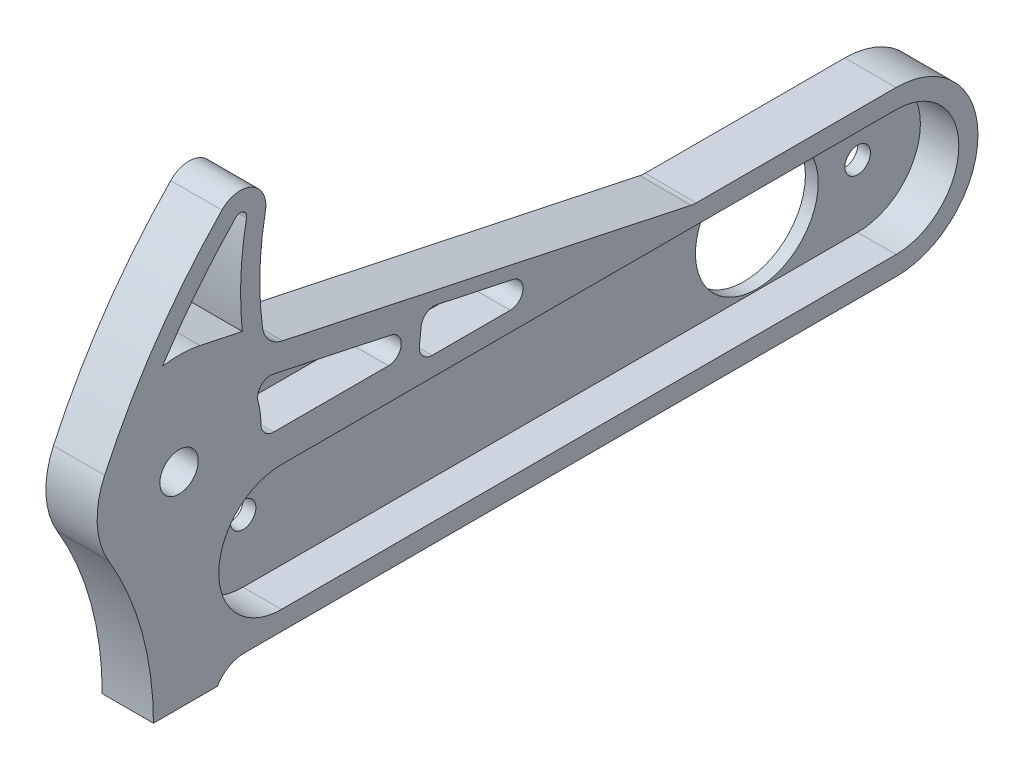
SolidWorks part; units mm, degrees
material "UHMW Polyethylene"
ref_plane "Front Plane" through (0, 0, 0) normal (0, 0, 1) x (1, 0, 0)
ref_plane "Top Plane" through (0, 0, 0) normal (0, 1, 0) x (1, 0, 0)
ref_plane "Right Plane" through (0, 0, 0) normal (1, 0, 0) x (0, 0, -1)
ref_plane "Plane1" through (44.45, 0, 0) normal (1, 0, 0) x (0, 0, -1)
sketch "Sketch1" plane through (44.45, 0, 0) normal (1, 0, 0) x (0, 0, -1)
  line L0 (0, 20.32) -> (-50.1918, 20.32)
  line L1 (-50.1918, 20.32) -> (-156.3872, 42.8925)
  line L2 (-184.15, -24.13) -> (-168.275, -24.13)
  line L3 (-177.8, -24.13) -> (-177.8, 26.67) construction
  line L4 (-161.6759, -20.32) -> (0, -20.32)
  line L5 (-210.1467, 95.3503) -> (7.8853, 24.145) construction
  line L6 (0, -25.4) -> (-249.5816, -25.4) construction
  arc A0 (-195.2627, 16.2798) -> (-196.2562, 35.1713) centre (-177.8, 26.67) cw
  arc A1 (-196.2562, 35.1713) -> (-167.1767, 77.5725) centre (-57.8348, -28.5883) cw
  arc A2 (-167.1767, 77.5725) -> (-156.3872, 71.9389) centre (-162.6208, 73.1492) cw
  arc A4 (-184.15, -24.13) -> (-195.2627, 16.2798) centre (-263.1786, -24.13) ccw
  arc A6 (-168.275, -24.13) -> (-161.6759, -20.32) centre (-161.6759, -27.94) cw
  arc A7 (0, -20.32) -> (0, 20.32) centre (0, 0) ccw
  circle A8 centre (0, 0) radius 25.4 construction
  circle A9 centre (-177.8, 26.67) radius 52.07 construction
  circle A10 centre (-161.6351, 76.1673) radius 3.175 construction
  arc A11 (-156.3872, 71.9389) -> (-156.3872, 42.8925) centre (-81.584, 57.4157) ccw
  circle A12 centre (-177.8, 26.67) radius 4.7625
  circle A13 centre (-152.4, 0) radius 3.175
  circle A14 centre (0, 0) radius 3.175
  circle A15 centre (-25.0031, 0) radius 15.22
  circle A17 centre (-25.0031, 0) radius 13.95 construction
  dimension "D1" = 6.35
  dimension "D2" = 152.4
  dimension "D3" = 76.2
  dimension "D6" = 7.62
  dimension "D9" = 5.08
  dimension "D10" = 31.75
  dimension "D12" = 9.525
  dimension "D13" = 6.35
  dimension "D8" = 1.27
  dimension "D4" = 15.875
  dimension "D5" = 6.35
  dimension "D7" = 12
  dimension "D11" = 1.27
extrude "Boss-Extrude1" add sketch "Sketch1" along normal blind 12.7
sketch "Sketch6" plane through (57.15, 0, 0) normal (1, 0, 0) x (0, 0, -1)
  line L0 (-35.4758, -20.32) -> (-14.5304, -20.32)
  line L1 (-35.4758, 20.32) -> (-14.5304, 20.32)
  line L2 (0, 20.32) -> (-50.1918, 20.32) construction
  line L3 (-161.6759, -20.32) -> (0, -20.32) construction
  arc A0 (-35.4758, -20.32) -> (-14.5304, -20.32) centre (-25.0031, 0) ccw
  circle A1 centre (-25.0031, 0) radius 15.22 construction
  arc A2 (-14.5304, 20.32) -> (-35.4758, 20.32) centre (-25.0031, 0) ccw
  dimension "D1" = 22.86
extrude "28mm motor support" [suppressed] add sketch "Sketch6" against normal up to surface (12.7 mm away) up to face at (44.45, 18.3967, 128.7869)
sketch "Sketch4" plane through (57.15, 0, 0) normal (1, 0, 0) x (0, 0, -1)
  line L0 (-157.7296, 23.495) -> (-95.6708, 23.495)
  line L1 (-95.6708, 23.495) -> (-160.4619, 37.2668)
  line L3 (-50.1918, 20.32) -> (-156.3872, 42.8925) construction
  line L4 (0, 20.32) -> (-50.1918, 20.32) construction
  arc A0 (-160.4619, 37.2668) -> (-157.7296, 23.495) centre (-177.8, 26.67) cw
  arc A2 (-196.2562, 35.1713) -> (-195.2627, 16.2798) centre (-177.8, 26.67) ccw construction
  dimension "D1" = 3.175
  dimension "D2" = 6.35
extrude "Cut-Extrude3" cut sketch "Sketch4" against normal offset from surface (10.16 mm away) 2.54 up to face at (44.45, 18.3967, 128.7869)
fillet "Fillet2" radius 3.175 3 edges at (52.07, 23.495, 95.6708) (52.07, 23.495, 157.7296) (52.07, 37.2668, 160.4619)
sketch "Sketch5" plane through (57.15, 0, 0) normal (1, 0, 0) x (0, 0, -1)
  line L0 (-113.9556, 30.6275) -> (-95.0107, 26.6006)
  line L1 (-95.6708, 20.32) -> (-115.0389, 20.32)
  line L2 (0, 20.32) -> (-50.1918, 20.32) construction
  line L3 (-50.1918, 20.32) -> (-156.3872, 42.8925) construction
  line L4 (-117.7733, 27.8537) -> (-118.1965, 23.8269)
  line L5 (-95.6708, 23.495) -> (-125.8789, 26.67) construction
  arc A0 (-113.9556, 30.6275) -> (-117.7733, 27.8537) centre (-114.6157, 27.5219) ccw
  arc A1 (-118.1965, 23.8269) -> (-115.0389, 20.32) centre (-115.0389, 23.495) ccw
  arc A2 (-95.6708, 20.32) -> (-95.0107, 26.6006) centre (-95.6708, 23.495) ccw
  arc A4 (-125.8789, 23.495) -> (-125.2188, 29.7756) centre (-125.8789, 26.67) ccw construction
  point P20 (-122.7213, 26.3381)
  dimension "D2" = 3.175
  dimension "D1" = 3.175
  dimension "D3" = 4.7625
extrude "Cut-Extrude4" cut sketch "Sketch5" against normal up to surface (10.16 mm away) up to face at (46.99, 28.5995, 145.7216)
sketch "Sketch2" plane through (57.15, 0, 0) normal (1, 0, 0) x (0, 0, -1)
  line L0 (-173.5752, 46.546) -> (-156.3872, 42.8925)
  line L1 (-172.5851, 51.2044) -> (-162.1055, 48.9769)
  arc A0 (-196.2562, 35.1713) -> (-173.5752, 46.546) centre (-177.8, 26.67) cw
  arc A1 (-196.2562, 35.1713) -> (-195.2627, 16.2798) centre (-177.8, 26.67) ccw construction
  arc A2 (-167.1767, 77.5725) -> (-196.2562, 35.1713) centre (-57.8348, -28.5883) ccw construction
  arc A3 (-156.3872, 71.9389) -> (-156.3872, 42.8925) centre (-81.584, 57.4157) ccw construction
  arc A4 (-156.3872, 71.9389) -> (-167.1767, 77.5725) centre (-162.6208, 73.1492) ccw construction
  arc A5 (-156.3872, 71.9389) -> (-156.3872, 42.8925) centre (-81.584, 57.4157) ccw
  arc A6 (-156.3872, 71.9389) -> (-167.1767, 77.5725) centre (-162.6208, 73.1492) ccw
  arc A7 (-167.1767, 77.5725) -> (-196.2562, 35.1713) centre (-57.8348, -28.5883) ccw
  arc A8 (-161.0624, 72.8466) -> (-162.1055, 48.9769) centre (-81.584, 57.4157) ccw
  arc A9 (-161.0624, 72.8466) -> (-163.7597, 74.255) centre (-162.6208, 73.1492) ccw
  arc A10 (-163.7597, 74.255) -> (-181.9186, 51.4121) centre (-57.8348, -28.5883) ccw
  arc A11 (-181.9186, 51.4121) -> (-172.5851, 51.2044) centre (-177.8, 26.67) cw
  dimension "D1" = 4.7625
extrude "Cut-Extrude1" cut sketch "Sketch2" against normal up to surface (12.7 mm away) contours A10 A11 L1 A8 A9 region at (57.15, 59.6657, 168.7495) up to face at (44.45, 18.3967, 128.7869)
sketch "Sketch3" plane through (57.15, 0, 0) normal (1, 0, 0) x (0, 0, -1)
  line L0 (-152.4, 15.5575) -> (0, 15.5575)
  line L1 (0, -15.5575) -> (-152.4, -15.5575)
  line L2 (0, 20.32) -> (-50.1918, 20.32) construction
  arc A0 (0, 15.5575) -> (0, -15.5575) centre (0, 0) cw
  arc A1 (-152.4, -15.5575) -> (-152.4, 15.5575) centre (-152.4, 0) cw
  arc A3 (0, -20.32) -> (0, 20.32) centre (0, 0) ccw construction
  circle A4 centre (-152.4, 0) radius 25.4 construction
  dimension "D1" = 4.7625
extrude "Cut-Extrude2" cut sketch "Sketch3" against normal offset from surface (9.525 mm away) 3.175 up to face at (44.45, 18.3967, 128.7869)
fillet "Fillet1" radius 6.35 2 edges at (50.8, 42.8925, 156.3872) (50.8, 20.32, 50.1918)
